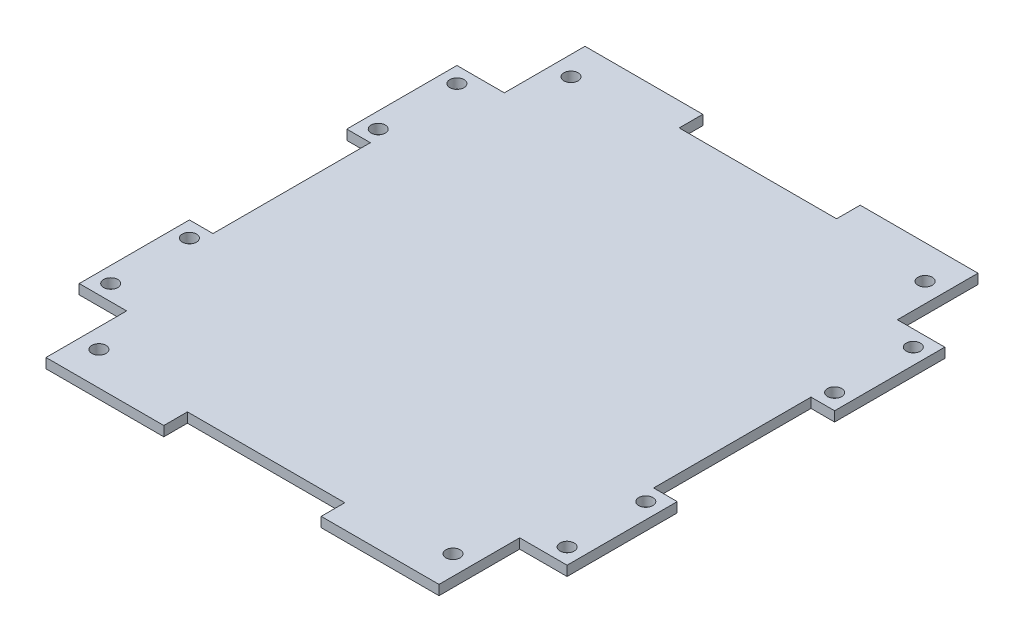
SolidWorks part; units mm, degrees
ref_plane "Front Plane" through (0, 0, 0) normal (0, 0, 1) x (1, 0, 0)
ref_plane "Top Plane" through (0, 0, 0) normal (0, 1, 0) x (1, 0, 0)
ref_plane "Right Plane" through (0, 0, 0) normal (1, 0, 0) x (0, 0, -1)
sketch "Sketch1" plane through (0, 0, 0) normal (0, 1, 0) x (1, 0, 0)
  line L0 (-25.4, 86.995) -> (-63.4314, 86.995)
  line L1 (-88.9, -101.6) -> (88.9, -101.6) construction
  line L2 (101.6, -88.9) -> (101.6, 88.9) construction
  line L3 (88.9, 101.6) -> (-88.9, 101.6) construction
  line L4 (-78.74, -60.96) -> (-63.4314, -60.96)
  line L5 (-63.4314, -60.96) -> (-63.4314, -86.995)
  line L6 (-63.4314, -86.995) -> (-25.4, -86.995)
  line L7 (63.4314, -86.995) -> (63.4314, -60.96)
  line L8 (63.4314, -60.96) -> (78.74, -60.96)
  line L9 (78.74, -60.96) -> (78.74, -25.4)
  line L10 (78.74, 60.96) -> (63.4314, 60.96)
  line L11 (63.4314, 60.96) -> (63.4314, 86.995)
  line L12 (63.4314, 86.995) -> (25.4, 86.995)
  line L13 (-63.4314, 86.995) -> (-63.4314, 60.96)
  line L14 (-63.4314, 60.96) -> (-78.74, 60.96)
  line L15 (-78.74, 60.96) -> (-78.74, 25.4)
  line L16 (-78.74, -25.4) -> (-78.74, -60.96)
  line L17 (-78.74, -25.4) -> (-71.12, -25.4)
  line L19 (-78.74, 25.4) -> (-71.12, 25.4)
  line L20 (-71.12, -25.4) -> (-71.12, 25.4)
  line L22 (-25.4, 86.995) -> (-25.4, 79.375)
  line L23 (-25.4, 79.375) -> (25.4, 79.375)
  line L24 (25.4, 86.995) -> (25.4, 79.375)
  line L25 (78.74, 25.4) -> (71.12, 25.4)
  line L27 (78.74, -25.4) -> (71.12, -25.4)
  line L28 (71.12, 25.4) -> (71.12, -25.4)
  line L30 (25.4, -86.995) -> (25.4, -79.375)
  line L31 (25.4, -79.375) -> (-25.4, -79.375)
  line L32 (-25.4, -86.995) -> (-25.4, -79.375)
  line L33 (78.74, 25.4) -> (78.74, 60.96)
  line L34 (25.4, -86.995) -> (63.4314, -86.995)
  line L35 (-101.6, 88.9) -> (-101.6, -88.9) construction
  arc A0 (88.9, -101.6) -> (101.6, -88.9) centre (88.9, -88.9) ccw construction
  arc A1 (-101.6, -88.9) -> (-88.9, -101.6) centre (-88.9, -88.9) ccw construction
  arc A2 (101.6, 88.9) -> (88.9, 101.6) centre (88.9, 88.9) ccw construction
  arc A3 (-101.6, 88.9) -> (-88.9, 101.6) centre (-88.9, 88.9) cw construction
  circle A4 centre (-57.15, 76.2) radius 2.286
  circle A5 centre (57.15, 76.2) radius 2.286
  circle A6 centre (57.15, -76.2) radius 2.286
  circle A7 centre (-57.15, -76.2) radius 2.286
  point P3 (0, 101.6)
  point P5 (101.6, 0)
  point P13 (101.6, 101.6)
  point P16 (-101.6, 101.6)
  point P38 (-71.12, 0)
  point P55 (0, -79.375)
  point P56 (0, 79.375)
  point P57 (71.12, 0)
  dimension "D2" = 12.7
  dimension "D11" = 4.572
  dimension "D8" = 44.45
  dimension "D1" = 203.2
  dimension "D3" = 203.2
  dimension "D4" = 22.86
  dimension "D5" = 15.3086
  dimension "D6" = 35.56
  dimension "D7" = 173.99
  dimension "D12" = 50.8
  dimension "D13" = 25.4
  dimension "D14" = 44.45
  dimension "D15" = 25.4
  dimension "D18" = 7.62
extrude "Boss-Extrude1" add sketch "Sketch1" along normal blind 3.175
sketch "Sketch2" plane through (0, 3.175, 0) normal (0, 1, 0) x (1, 0, 0)
  line L0 (0, -1000) -> (0, 49000) construction
  line L1 (-1000, 0) -> (49000, 0) construction
  line L2 (-78.74, -60.96) -> (-63.4314, -60.96) construction
  line L3 (-71.12, -25.4) -> (-78.74, -25.4) construction
  line L4 (-78.74, -25.4) -> (-78.74, -60.96) construction
  circle A0 centre (-73.66, -30.48) radius 2.286
  circle A1 centre (-73.66, -55.88) radius 2.286
  circle A2 centre (73.66, -55.88) radius 2.286
  circle A3 centre (73.66, -30.48) radius 2.286
  circle A4 centre (73.66, 30.48) radius 2.286
  circle A5 centre (73.66, 55.88) radius 2.286
  circle A6 centre (-73.66, 55.88) radius 2.286
  circle A7 centre (-73.66, 30.48) radius 2.286
  dimension "D1" = 4.572
  dimension "D2" = 5.08
  dimension "D3" = 5.08
  dimension "D4" = 5.08
extrude "Cut-Extrude1" cut sketch "Sketch2" against normal through all
